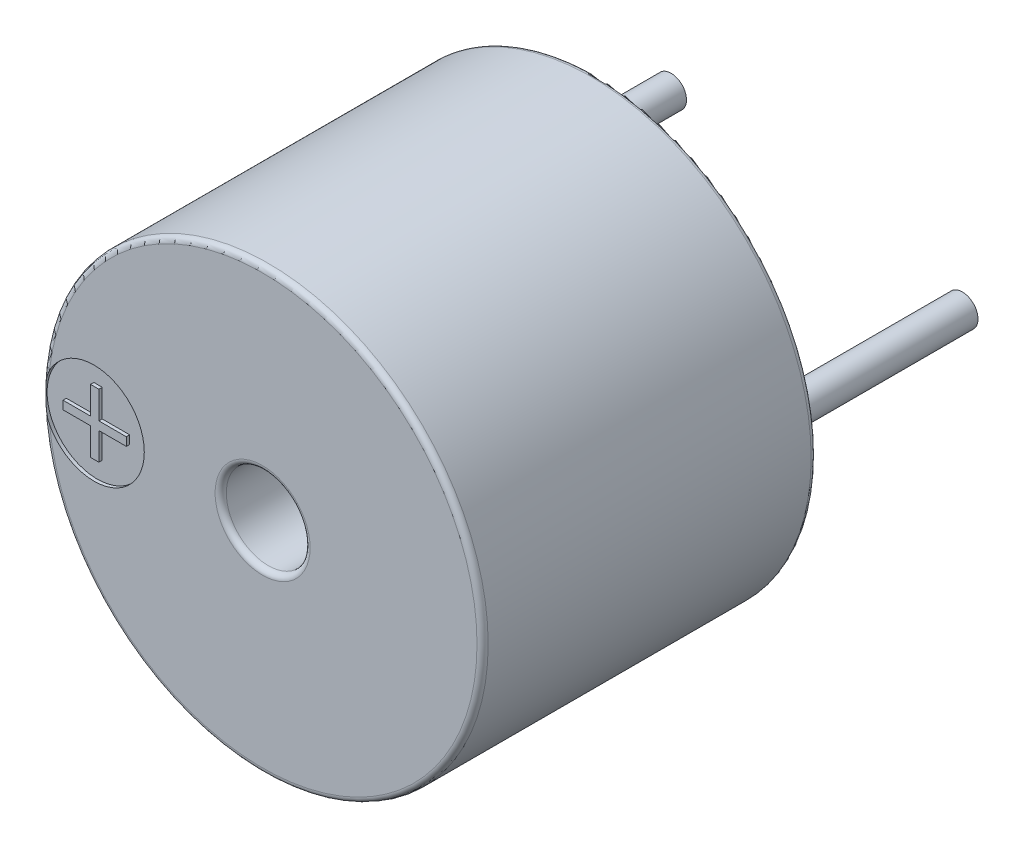
SolidWorks part; units mm, degrees
ref_plane "Front Plane" through (0, 0, 0) normal (0, 0, 1) x (1, 0, 0)
ref_plane "Top Plane" through (0, 0, 0) normal (0, 1, 0) x (1, 0, 0)
ref_plane "Right Plane" through (0, 0, 0) normal (1, 0, 0) x (0, 0, -1)
sketch "Sketch2" plane through (0, 0, 0) normal (0, 0, 1) x (1, 0, 0)
  circle A0 centre (0, 0) radius 5
  dimension "D1" = 10
extrude "Boss-Extrude1" add sketch "Sketch2" along normal blind 7.5946
sketch "Sketch3" plane through (0, 0, 7.5946) normal (0, 0, 1) x (1, 0, 0)
  circle A0 centre (0, 0) radius 0.9525
  dimension "D1" = 1.905
extrude "Cut-Extrude1" cut sketch "Sketch3" against normal blind 2.54
fillet "Fillet1" radius 0.127 3 edges at (0.9525, 0, 7.5946) (5, 0, 0) (5, 0, 7.5946)
sketch "Sketch4" plane through (0, 0, 0) normal (0, 0, -1) x (-1, 0, 0)
  line L0 (-3.81, 0) -> (3.81, 0) construction
  circle A1 centre (3.81, 0) radius 0.35
  point P3 (-3.81, 0)
  point P4 (3.81, 0)
  dimension "D4" = 0.7
  dimension "D1" = 7.62
  dimension "D2" = 3.81
extrude "Boss-Extrude2" add sketch "Sketch4" along normal blind 5.5
sketch "Sketch7" plane through (0, 0, 0) normal (0, 0, -1) x (-1, 0, 0)
  line L0 (0, 0) -> (-5.9283, 0) construction
  circle A0 centre (-3.81, 0) radius 0.3556
  dimension "D1" = 0.7112
  dimension "D2" = 3.81
extrude "Boss-Extrude3" add sketch "Sketch7" along normal blind 4.5
ref_axis "Axis1" through (3.81, 0, -4.5) along (0, 0, 1)
ref_axis "Axis2" through (-3.81, 0, -5.5) along (0, 0, 1)
ref_plane "Plane1" through (0, 0, 0) normal (0, 1, 0) x (-1, 0, 0)
sketch "Sketch6" plane through (0, 0, 7.5946) normal (0, 0, 1) x (1, 0, 0)
  line L0 (8.0437, 0) -> (-8.0437, 0) construction
  circle A0 centre (-3.8325, 0) radius 1.143
  text T0 "+" font "Century Gothic" height in points 8
  dimension "D1" = 2.286
  dimension "D2" = 1.0414
  dimension "D3" = 0.889
extrude "Cut-Extrude3" cut sketch "Sketch6" against normal blind 0.0762
ref_plane "Plane2" [suppressed] through (3.81, 0, 0) normal (1, 0, 0) x (0, 0, -1)
ref_plane "Plane3" [suppressed] through (-3.81, 0, 0) normal (1, 0, 0) x (0, 0, -1)
